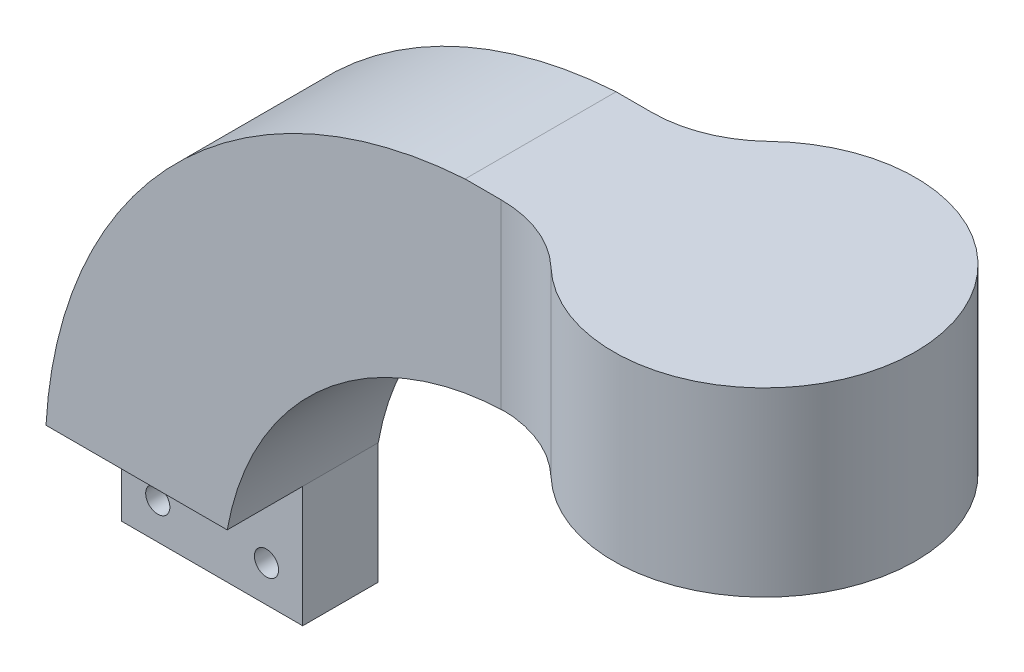
SolidWorks part; units mm, degrees
material "ABS"
ref_plane "Front Plane" through (0, 0, 0) normal (0, 0, 1) x (1, 0, 0)
ref_plane "Top Plane" through (0, 0, 0) normal (0, 1, 0) x (1, 0, 0)
ref_plane "Right Plane" through (0, 0, 0) normal (1, 0, 0) x (0, 0, -1)
sketch "Sketch1" plane through (0, 0, 0) normal (0, 0, 1) x (1, 0, 0)
  line L0 (69.3749, 90) -> (120, 90)
  line L1 (0, 0) -> (30, 0)
  line L2 (0, 0) -> (0, 20)
  line L3 (20, 90) -> (30, 90)
  line L4 (30, 0) -> (30, 20)
  line L5 (20, 90) -> (30, 90)
  line L7 (76.2846, 60) -> (120, 60)
  line L8 (120, 90) -> (120, 60)
  arc A1 (30, 20) -> (79.2135, 60) centre (77.7491, 11.5271) cw
  arc A2 (0, 20) -> (78.8823, 90) centre (74.1286, 15.9111) cw
  dimension "D4" = 20
  dimension "D5" = 20
  dimension "D1" = 30
  dimension "D2" = 30
  dimension "D3" = 90
extrude "Boss-Extrude1" add sketch "Sketch1" along normal blind 25 contours L2 L1 L4 L7 L8 L5 L3 region at (51.6447, 55.6367, 0)
sketch "Sketch3" plane through (0, 90, 0) normal (0, 1, 0) x (1, 0, 0)
  line L0 (120, -12.5) -> (92.8851, -12.5) construction
  line L1 (120, -25) -> (120, 0) construction
  line L2 (69.3749, 0) -> (69.3749, -25)
  line L3 (69.3749, -25) -> (75.3178, -25)
  line L4 (69.3749, -25) -> (120, -25) construction
  line L5 (69.3749, 0) -> (75.3178, 0)
  line L6 (69.3749, 0) -> (120, 0) construction
  arc A0 (89.151, -30.5556) -> (89.151, 5.5556) centre (106.4426, -12.5) ccw
  arc A1 (75.3178, -25) -> (89.151, -30.5556) centre (75.3178, -45) cw
  arc A2 (75.3178, 0) -> (89.151, 5.5556) centre (75.3178, 20) ccw
  point P17 (84.7919, -25)
  point P20 (84.7919, 0)
  dimension "D1" = 50
  dimension "D2" = 20
extrude "Boss-Extrude3" add sketch "Sketch3" against normal up to surface (30 mm away) up to face at (99.6068, 60, 12.5)
ref_axis "Axis1" through (106.4426, 60, 12.5) along (0, 1, 0)
sketch "Sketch4" plane through (0, 0, 0) normal (1, 0, 0) x (0, 0, -1)
  line L0 (-25, 0) -> (0, 0) construction
  line L1 (-12.5, 0) -> (-42.5, 0)
  line L2 (-12.5, 0) -> (-12.5, 20)
  line L3 (-12.5, 20) -> (-42.5, 20)
  line L4 (-42.5, 0) -> (-42.5, 20)
  dimension "D1" = 30
  dimension "D2" = 20
extrude "Cut-Extrude1" cut sketch "Sketch4" along normal blind 49
sketch "Sketch5" plane through (0, 0, 12.5) normal (0, 0, 1) x (1, 0, 0)
  line L0 (30, 14) -> (0, 14) construction
  line L1 (30, 20) -> (30, 0) construction
  line L2 (0, 20) -> (0, 0) construction
  line L3 (30, 20) -> (0, 20) construction
  line L4 (30, 6) -> (0, 6) construction
  line L6 (30, 0) -> (0, 0) construction
  line L7 (0, 0) -> (0, 20) construction
  line L8 (30, 0) -> (30, 20) construction
  circle A0 centre (24, 6) radius 2
  circle A1 centre (6, 6) radius 2
  circle A2 centre (15, 14) radius 2
  dimension "D2" = 4
  dimension "D3" = 4
  dimension "D4" = 4
  dimension "D1" = 6
  dimension "D5" = 15
  dimension "D6" = 6
  dimension "D7" = 6
  dimension "D8" = 6
extrude "Cut-Extrude2" cut sketch "Sketch5" against normal blind 49
